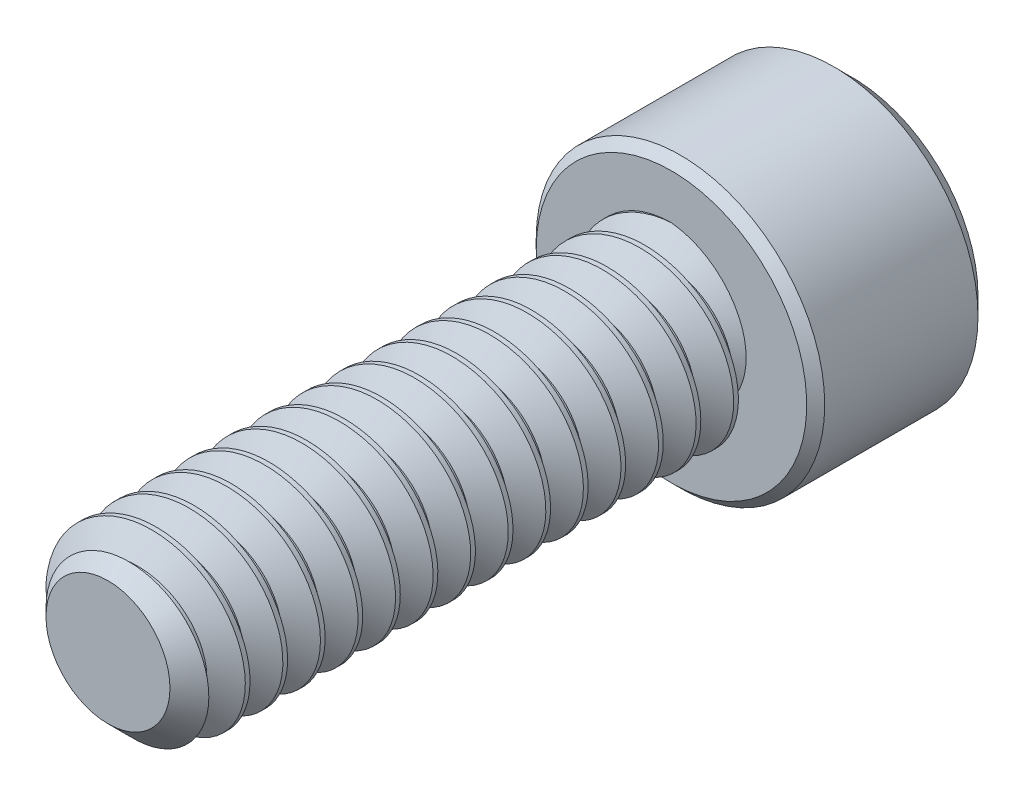
SolidWorks part; units mm, degrees
ref_plane "Front Plane" through (0, 0, 0) normal (0, 0, 1) x (1, 0, 0)
ref_plane "Top Plane" through (0, 0, 0) normal (0, 1, 0) x (1, 0, 0)
ref_plane "Right Plane" through (0, 0, 0) normal (1, 0, 0) x (0, 0, -1)
sketch "Sketch1" plane through (0, 0, 0) normal (0, 0, 1) x (1, 0, 0)
  line L0 (0, 0.762) -> (0, -0.762) construction
  circle A0 centre (0, 0) radius 0.762
  dimension "OD" = 1.524
extrude "Extrude1" add sketch "Sketch1" against normal blind 4.7625
sketch "Sketch2" plane through (0, 0, 0) normal (0, 0, 1) x (1, 0, 0)
  circle A0 centre (0, 0) radius 0.762 construction
  circle A1 centre (0, 0) radius 0.762
curve "Helix/Spiral1" pitch 0.3175 height 5.08 radius 0.762 centre (0, 0, 0) axis (0, 0, -1) start towards (0, 1, 0) parameters "pitch"=0.3175
chamfer "Chamfer3" distance 0.2381 angle 45 1 edges at (0.762, 0, 0)
sketch "Sketch3" plane through (0, 0, 0) normal (1, 0, 0) x (0, 0, -1)
  line L0 (-0.2778, 0.762) -> (-0.1588, 0.5558)
  line L1 (-0.1588, 0.5558) -> (-0.1191, 0.5558)
  line L2 (-0.1191, 0.5558) -> (0, 0.762)
  line L3 (-0.2778, 0.762) -> (0, 0.762)
  line L4 (-0.1389, 0.762) -> (-0.1389, 0.5558) construction
  line L5 (-0.2183, 0.6589) -> (-0.0595, 0.6589) construction
  line L6 (0, 0.762) -> (0, -0.762) construction
  dimension "D1" = 0.0397
  dimension "D2" = 0.1588
  dimension "D3" = 60
sweep "Cut-Sweep1" cut profiles "Sketch3" path "Helix/Spiral1"
sketch "Sketch6" plane through (0, 0, -4.7625) normal (0, 0, -1) x (-1, 0, 0)
  circle A0 centre (0, 0) radius 1.2192
  dimension "head dia" = 2.4384
extrude "Extrude2" add sketch "Sketch6" along normal blind 1.524
sketch "Sketch7" plane through (0, 0, -6.2865) normal (0, 0, -1) x (-1, 0, 0)
  line L1 (0, 0.7332) -> (-0.635, 0.3666)
  line L2 (-0.635, 0.3666) -> (-0.635, -0.3666)
  line L3 (-0.635, -0.3666) -> (0, -0.7332)
  line L4 (0, -0.7332) -> (0.635, -0.3666)
  line L5 (0.635, -0.3666) -> (0.635, 0.3666)
  line L6 (0.635, 0.3666) -> (0, 0.7332)
  circle A0 centre (0, 0) radius 0.635 construction
  dimension "hex dia" = 1.27
extrude "Cut-Extrude1" cut sketch "Sketch7" against normal blind 0.9525
sketch "Sketch8" plane through (0, 0, -6.2865) normal (0, 0, -1) x (-1, 0, 0)
  circle A0 centre (0, 0) radius 0.7332
extrude "Cut-Extrude2" cut sketch "Sketch8" against normal blind 0.1524 draft 45
chamfer "Chamfer1" distance 0.1524 angle 45 1 edges at (-1.2192, 0, -6.2865)
chamfer "Chamfer2" distance 0.0762 angle 45 1 edges at (-1.2192, 0, -4.7625)
sketch "Sketch9" plane through (0, 0, 0) normal (1, 0, 0) x (0, 0, -1)
  line L0 (0, 0.762) -> (0, -0.762) construction
  line L1 (1.7463, 0.762) -> (1.7463, -0.762) construction
  line L2 (4.7625, 1.2192) -> (4.7625, -1.2192) construction
  line L3 (6.2865, 1.2192) -> (6.2865, -1.2192) construction
  line L4 (6.2865, 0) -> (0, 0) construction
  dimension "D1" = 1.7463
  dimension "D2" = 1.524
  dimension "D3" = 2.4384
  dimension "D4" = 0.635
  dimension "D5" = 0.3302
equation "\"D3@Helix/Spiral1\" = \"screw length@Extrude1\"+\"pitch@Helix/Spiral1\""
equation "\"D1@Sketch3\" = \"pitch@Helix/Spiral1\"*.125"
equation "\"D2@Sketch3\" = \"pitch@Helix/Spiral1\"*.5"
equation "\"D1@Cut-Extrude1\" = \"hex dia@Sketch7\"*.75"
equation "\"D1@Chamfer1\" = \"head depth@Extrude2\"/10"
equation "\"D1@Sketch9\" = \"pitch@Helix/Spiral1\"*5.5"
equation "\"D1@Chamfer2\" = \"D1@Chamfer1\"/2"
equation "\"D1@Cut-Extrude2\" = \"D1@Chamfer2\"*2"
equation "\"D1@Chamfer3\" = \"pitch@Helix/Spiral1\"*.750"
equation "\"D2@Sketch9\" = \"head depth@Extrude2\""
equation "\"D3@Sketch9\" = \"head dia@Sketch6\""
equation "\"D4@Sketch9\" = \"screw length@Extrude1\""
